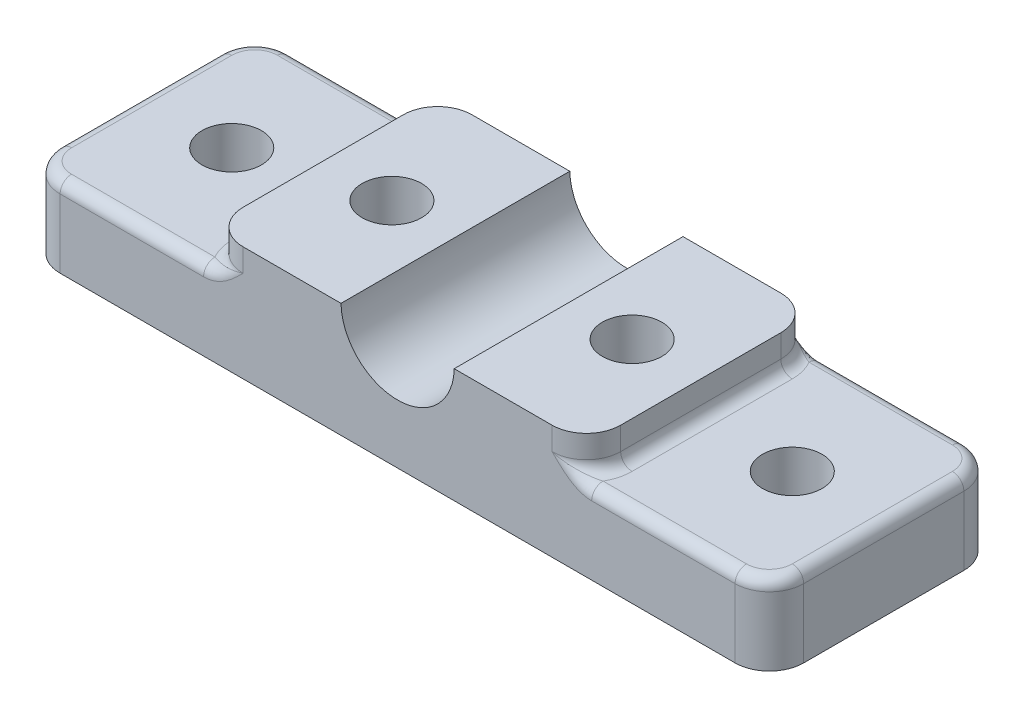
SolidWorks part; units mm, degrees
material "ABS"
ref_plane "Front Plane" through (0, 0, 0) normal (0, 0, 1) x (1, 0, 0)
ref_plane "Top Plane" through (0, 0, 0) normal (0, 1, 0) x (1, 0, 0)
ref_plane "Right Plane" through (0, 0, 0) normal (1, 0, 0) x (0, 0, -1)
sketch "Sketch1" plane through (0, 0, 0) normal (0, 1, 0) x (1, 0, 0)
  line L0 (-50.7915, 0) -> (50.7915, 0) construction
  line L1 (0, 10) -> (0, -10) construction
  line L2 (-29.5, -10) -> (29.5, -10)
  line L3 (-32.5, -7) -> (-32.5, 7)
  line L4 (-29.5, 10) -> (29.5, 10)
  line L5 (32.5, -7) -> (32.5, 7)
  line L6 (-32.5, -10) -> (32.5, 10) construction
  line L7 (-32.5, 10) -> (32.5, -10) construction
  line L8 (-16.5, -10) -> (16.5, -10) construction
  line L9 (-16.5, -10) -> (-16.5, 10) construction
  line L10 (-16.5, 10) -> (16.5, 10) construction
  line L11 (16.5, -10) -> (16.5, 10) construction
  line L12 (-16.5, -10) -> (16.5, 10) construction
  line L13 (-16.5, 10) -> (16.5, -10) construction
  arc A0 (-32.5, -7) -> (-29.5, -10) centre (-29.5, -7) ccw
  arc A1 (29.5, -10) -> (32.5, -7) centre (29.5, -7) ccw
  arc A2 (32.5, 7) -> (29.5, 10) centre (29.5, 7) ccw
  arc A3 (-29.5, 10) -> (-32.5, 7) centre (-29.5, 7) ccw
  circle A4 centre (-10.5, 0) radius 2.6
  circle A5 centre (-24.5, 0) radius 2.6
  circle A6 centre (24.5, 0) radius 2.6
  circle A7 centre (10.5, 0) radius 2.6
  point P3 (0, 0)
  point P4 (0, 0)
  point P25 (0, 0)
  dimension "D3" = 3
  dimension "D4" = 5.2
  dimension "D7" = 14
  dimension "D1" = 65
  dimension "D2" = 20
  dimension "D5" = 33
  dimension "D6" = 10.5
extrude "Boss-Extrude1" add sketch "Sketch1" along normal blind 7
sketch "Sketch2" plane through (0, 7, 0) normal (0, 1, 0) x (1, 0, 0)
  line L0 (29.5, 10) -> (-29.5, 10) construction
  line L1 (-13.5, -10) -> (13.5, -10)
  line L2 (-16.5, -7) -> (-16.5, 7)
  line L3 (-13.5, 10) -> (13.5, 10)
  line L4 (16.5, -7) -> (16.5, 7)
  line L5 (-16.5, -10) -> (16.5, 10) construction
  line L6 (-16.5, 10) -> (16.5, -10) construction
  arc A0 (13.5, 10) -> (16.5, 7) centre (13.5, 7) cw
  arc A1 (16.5, -7) -> (13.5, -10) centre (13.5, -7) cw
  arc A2 (-13.5, -10) -> (-16.5, -7) centre (-13.5, -7) cw
  arc A3 (-16.5, 7) -> (-13.5, 10) centre (-13.5, 7) cw
  circle A4 centre (-10.5, 0) radius 2.6 construction
  circle A5 centre (10.5, 0) radius 2.6 construction
  circle A6 centre (-10.5, 0) radius 2.6
  circle A7 centre (10.5, 0) radius 2.6
  point P0 (0, 0)
  dimension "D2" = 3
  dimension "D1" = 33
extrude "Boss-Extrude2" add sketch "Sketch2" along normal blind 3
sketch "Sketch3" plane through (0, 0, 10) normal (0, 0, 1) x (1, 0, 0)
  line L0 (0, 0) -> (0, 16.2371) construction
  line L1 (-29.5, 0) -> (29.5, 0) construction
  circle A0 centre (0, 10.1) radius 4.95
  dimension "D1" = 9.9
  dimension "D2" = 10.1
extrude "Cut-Extrude1" cut sketch "Sketch3" against normal up to surface (20 mm away) up to face at (2, 6.375, -10)
sketch "Sketch4" plane through (0, 0, 0) normal (0, -1, 0) x (1, 0, 0)
  line L0 (-32.5, -7) -> (-32.5, 7) construction
  line L1 (-10.5, 4.6188) -> (-14.5, 2.3094)
  line L2 (-14.5, 2.3094) -> (-14.5, -2.3094)
  line L3 (-14.5, -2.3094) -> (-10.5, -4.6188)
  line L4 (-10.5, -4.6188) -> (-6.5, -2.3094)
  line L5 (-6.5, -2.3094) -> (-6.5, 2.3094)
  line L6 (-6.5, 2.3094) -> (-10.5, 4.6188)
  line L7 (14.5, 2.3094) -> (10.5, 4.6188)
  line L8 (10.5, 4.6188) -> (6.5, 2.3094)
  line L9 (6.5, 2.3094) -> (6.5, -2.3094)
  line L10 (6.5, -2.3094) -> (10.5, -4.6188)
  line L11 (10.5, -4.6188) -> (14.5, -2.3094)
  line L12 (14.5, -2.3094) -> (14.5, 2.3094)
  line L13 (32.5, 7) -> (32.5, -7) construction
  circle A0 centre (-10.5, 0) radius 4 construction
  circle A1 centre (10.5, 0) radius 4 construction
  dimension "D1" = 8
extrude "Cut-Extrude2" cut sketch "Sketch4" against normal blind 5
fillet "Fillet1" radius 1 16 edges at (-16.5, 7, 0) (16.5, 7, 0) (31.6213, 7, -9.1213) (32.5, 7, 0) (-31.6213, 7, -9.1213) (-32.5, 7, 0) (31.6213, 7, 9.1213) (-31.6213, 7, 9.1213)
